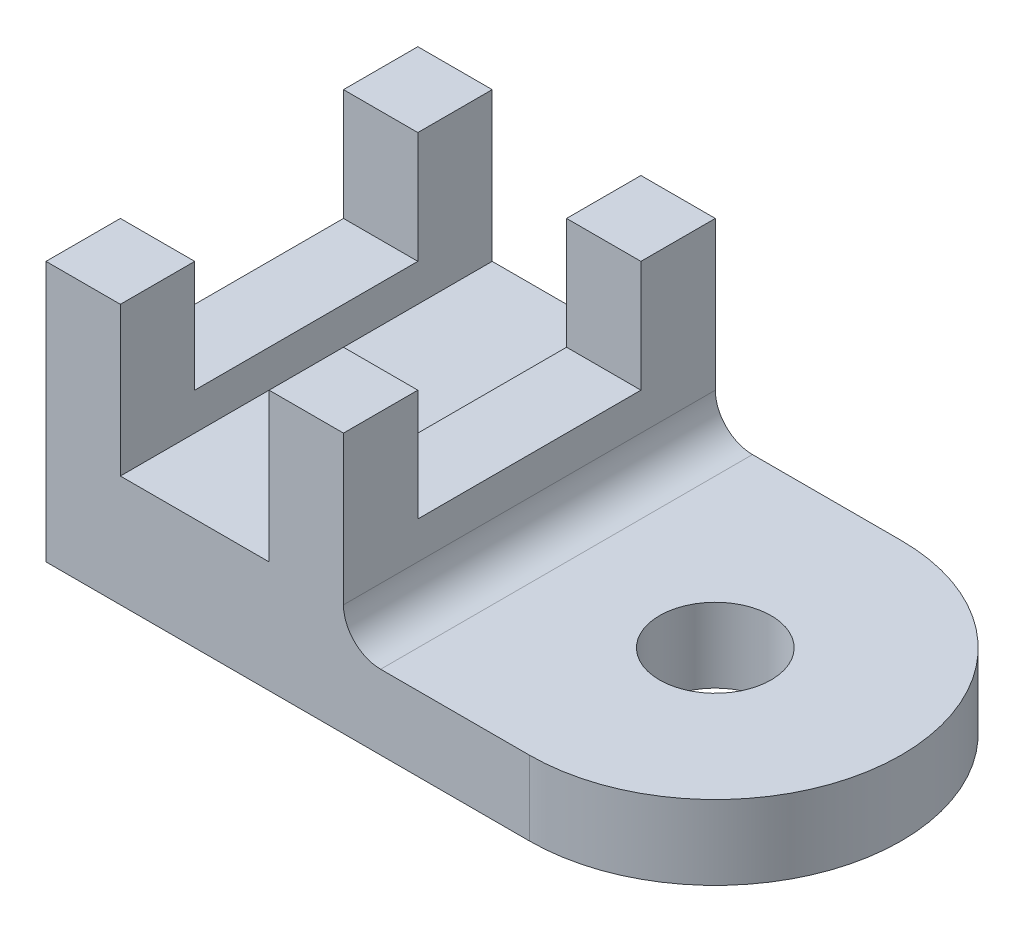
SolidWorks part; units mm, degrees
material "1060 Alloy"
ref_plane "Front Plane" through (0, 0, 0) normal (0, 0, 1) x (1, 0, 0)
ref_plane "Top Plane" through (0, 0, 0) normal (0, 1, 0) x (1, 0, 0)
ref_plane "Right Plane" through (0, 0, 0) normal (1, 0, 0) x (0, 0, -1)
sketch "Sketch1" plane through (0, 0, 0) normal (0, 1, 0) x (1, 0, 0)
  line L0 (50.8, 63.5) -> (50.8, 0)
  line L1 (0, 0) -> (82.55, 0)
  line L2 (0, 0) -> (0, 63.5)
  line L3 (0, 63.5) -> (82.55, 63.5)
  line L4 (82.55, 0) -> (82.55, 63.5)
  circle A1 centre (82.55, 31.75) radius 31.75
  circle A2 centre (82.55, 31.75) radius 9.525
  dimension "D3" = 63.5
  dimension "D4" = 19.05
  dimension "D1" = 63.5
  dimension "D2" = 82.55
  dimension "D5" = 31.75
extrude "Boss-Extrude1" add sketch "Sketch1" along normal blind 12.7 contours A1 L3 L0 | A1 L0 L1 | A2 L4 A1 | A2 L4 A1 region at (57.8919, 0, -56.4081) region at (57.8919, 0, -7.0919) region at (68.142, 0, -31.75) region at (96.958, 0, -31.75)
extrude "Boss-Extrude2" add sketch "Sketch1<4>" along normal blind 19.05 contours L3 L2 L1 L0 region at (25.4, 0, -31.75)
sketch "Sketch1<4>" plane through (0, 0, 0) normal (0, 1, 0) x (1, 0, 0) same geometry as "Sketch1"
sketch "Sketch6" plane through (0, 19.05, 0) normal (0, 1, 0) x (1, 0, 0)
  line L0 (0, 0) -> (50.8, 0) construction
  line L1 (0, 63.5) -> (12.7, 63.5)
  line L2 (0, 63.5) -> (0, 0)
  line L3 (0, 0) -> (12.7, 0)
  line L4 (12.7, 63.5) -> (12.7, 0)
  line L6 (0, 50.8) -> (12.7, 50.8)
  line L7 (0, 50.8) -> (0, 12.7)
  line L8 (0, 12.7) -> (12.7, 12.7)
  line L9 (12.7, 50.8) -> (12.7, 12.7)
  line L10 (50.8, 63.5) -> (38.1, 63.5)
  line L11 (50.8, 63.5) -> (50.8, 0)
  line L12 (50.8, 0) -> (38.1, 0)
  line L13 (38.1, 63.5) -> (38.1, 0)
  line L14 (38.1, 50.8) -> (50.8, 50.8)
  line L15 (38.1, 50.8) -> (38.1, 12.7)
  line L16 (38.1, 12.7) -> (50.8, 12.7)
  line L17 (50.8, 50.8) -> (50.8, 12.7)
  line M17 (50.8, 63.5) -> (0, 63.5)
  line M18 (0, 63.5) -> (0, 0)
  line M19 (0, 0) -> (50.8, 0)
  line M20 (50.8, 0) -> (50.8, 63.5)
  dimension "D1" = 12.7
  dimension "D2" = 12.7
  dimension "D3" = 12.7
  dimension "D4" = 12.7
  dimension "D5" = 12.7
  dimension "D6" = 12.7
extrude "Boss-Extrude3" add sketch "Sketch6" along normal blind 25.4 contours L6 L4 M18 M17 | L8 L4 M18 M19 | L13 L14 L11 M17 | L16 L13 M19 M20 region at (6.35, 19.05, -57.15) region at (44.45, 19.05, -57.15) region at (6.35, 19.05, -6.35) region at (44.45, 19.05, -6.35)
extrude "Boss-Extrude4" add sketch "Sketch6<3>" along normal blind 6.35 contours L2 L8 L4 L6 | L13 L16 L11 L14 region at (6.35, 19.05, -31.75) region at (44.45, 19.05, -31.75)
sketch "Sketch6<3>" plane through (0, 19.05, 0) normal (0, 1, 0) x (1, 0, 0) same geometry as "Sketch6"
fillet "Fillet1" radius 6.35 1 edges at (50.8, 12.7, -31.75)
